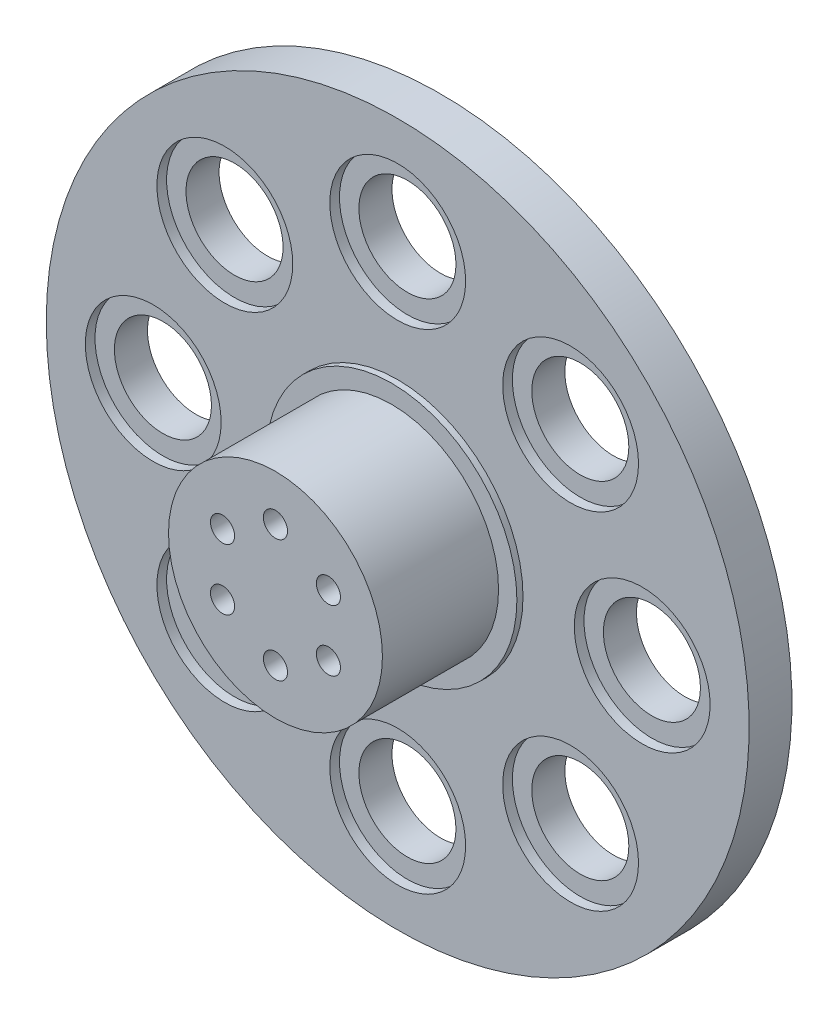
SolidWorks part; units mm, degrees
material "PETG"
ref_plane "Front Plane" through (0, 0, 0) normal (0, 0, 1) x (1, 0, 0)
ref_plane "Top Plane" through (0, 0, 0) normal (0, 1, 0) x (1, 0, 0)
ref_plane "Right Plane" through (0, 0, 0) normal (1, 0, 0) x (0, 0, -1)
sketch "Sketch1" plane through (0, 0, 0) normal (0, 0, 1) x (1, 0, 0)
  circle A0 centre (0, 0) radius 17.5
  dimension "D1" = 35
extrude "Boss-Extrude1" add sketch "Sketch1" along normal blind 19
sketch "Sketch7" plane through (0, 0, 0) normal (0, 0, -1) x (-1, 0, 0)
  circle A0 centre (0, 0) radius 20.5
  dimension "D1" = 41
extrude "Boss-Extrude3" add sketch "Sketch7" along normal blind 1
sketch "Sketch3" plane through (0, 0, -1) normal (0, 0, -1) x (-1, 0, 0)
  circle A0 centre (0, 0) radius 57.5
  dimension "D1" = 115
extrude "Boss-Extrude2" add sketch "Sketch3" along normal blind 7
sketch "Sketch4" plane through (0, 0, -8) normal (0, 0, -1) x (-1, 0, 0)
  circle A0 centre (0, 0) radius 11
  dimension "D1" = 22
extrude "Cut-Extrude1" cut sketch "Sketch4" against normal blind 7
sketch "Sketch5" plane through (0, 0, -1) normal (0, 0, -1) x (-1, 0, 0)
  circle A0 centre (0, 0) radius 7.5
  dimension "D1" = 15
extrude "Cut-Extrude2" cut sketch "Sketch5" against normal blind 0.5
sketch "Sketch6" plane through (0, 0, 19) normal (0, 0, 1) x (1, 0, 0)
  circle A0 centre (0, 10) radius 1.975
  dimension "D1" = 3.95
  dimension "D2" = 10
extrude "Cut-Extrude3" cut sketch "Sketch6" against normal blind 10
pattern_circular "CirPattern1" count 6 over 360 about axis through (0, 0, 19) along (0, 0, 1) of "Cut-Extrude3"
sketch "Sketch8" plane through (0, 0, -1) normal (0, 0, 1) x (1, 0, 0)
  circle A0 centre (0, 0) radius 40 construction
  circle A1 centre (-40, 0) radius 7.94
  circle A2 centre (-28.2843, 28.2843) radius 7.94
  circle A3 centre (0, 40) radius 7.94
  circle A4 centre (28.2843, 28.2843) radius 7.94
  circle A5 centre (40, 0) radius 7.94
  circle A6 centre (28.2843, -28.2843) radius 7.94
  circle A7 centre (0, -40) radius 7.94
  circle A8 centre (-28.2843, -28.2843) radius 7.94
  dimension "D1" = 80
  dimension "D2" = 15.88
  dimension "D3" = 8
extrude "Cut-Extrude4" cut sketch "Sketch8" against normal through all
sketch "Sketch9" plane through (0, 0, -1) normal (0, 0, 1) x (1, 0, 0)
  line L0 (0, 0) -> (0, 40) construction
  circle A0 centre (0, 40) radius 11.1125
  circle A1 centre (0, 40) radius 7.94 construction
  circle A2 centre (28.2843, 28.2843) radius 11.1125
  circle A3 centre (40, 0) radius 11.1125
  circle A4 centre (28.2843, -28.2843) radius 11.1125
  circle A5 centre (0, -40) radius 11.1125
  circle A6 centre (-28.2843, -28.2843) radius 11.1125
  circle A7 centre (-40, 0) radius 11.1125
  circle A8 centre (-28.2843, 28.2843) radius 11.1125
  point P17 (0, 0)
  dimension "D1" = 22.225
  dimension "D2" = 8
extrude "Cut-Extrude5" cut sketch "Sketch9" against normal blind 1.5875
chamfer "Chamfer1" distance 1 angle 45 1 edges at (-11, 0, -8)
equation "\"N\"= 21"
equation "\"R\"= 65mm"
equation "\"E\" = ROUND(\"R\" / \"N\" * 0.7, 2)"
equation "\"R_r\" = ( 1in / 2 ) / 2"
equation "\"D_p\" = 8cm"
equation "\"D1@Sketch8\"=\"D_p\""
equation "\"N_p\"= 8"
equation "\"D3@Sketch8\"=\"N_p\""
